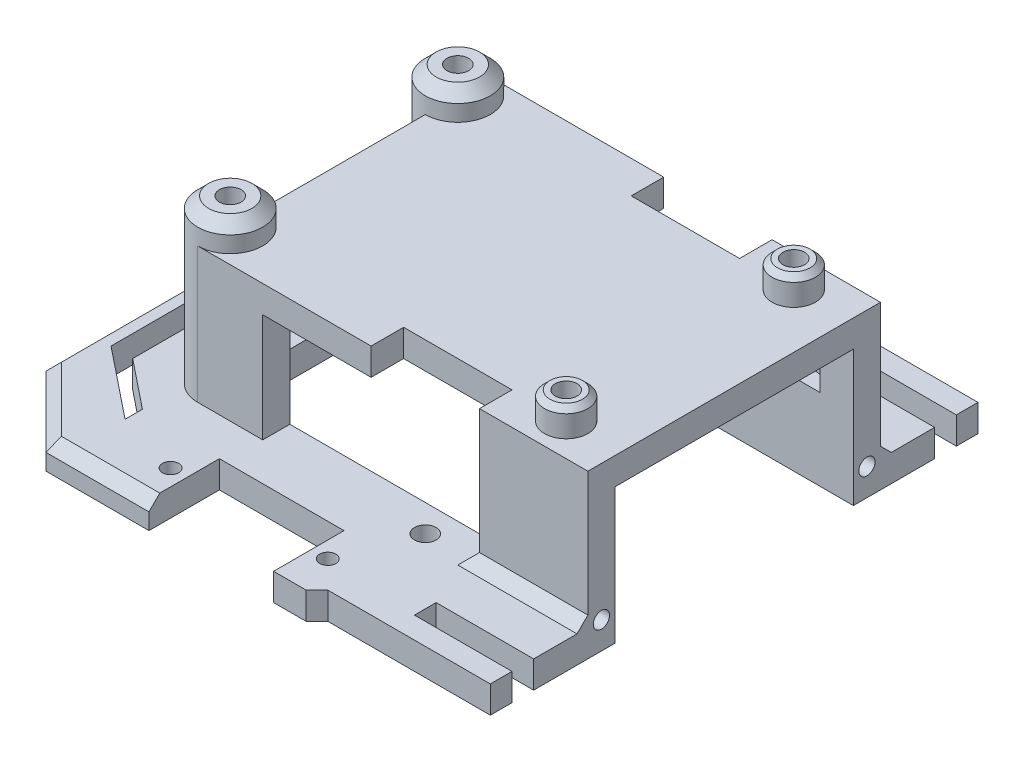
SolidWorks part; units mm, degrees
note: The reader was unsure of these and kept them because the rebuilt part matched: shared geometry of "Sketch13<3>", "Sketch13<5>".
material "Plain Carbon Steel"
ref_plane "Front Plane" through (0, 0, 0) normal (0, 0, 1) x (1, 0, 0)
ref_plane "Top Plane" through (0, 0, 0) normal (0, 1, 0) x (1, 0, 0)
ref_plane "Right Plane" through (0, 0, 0) normal (1, 0, 0) x (0, 0, -1)
sketch "Sketch1" plane through (0, 0, 0) normal (0, 1, 0) x (1, 0, 0)
  line L0 (0, 0) -> (148.3177, 0) construction
  line L1 (0, 34) -> (0, -34)
  line L2 (0, -34) -> (13, -47)
  line L3 (13, -47) -> (32, -47)
  line L4 (32, -47) -> (32, -34)
  line L5 (32, -34) -> (55, -34)
  line L6 (55, -34) -> (55, -47)
  line L7 (55, -47) -> (61, -47)
  line L8 (61, -47) -> (63, -45)
  line L9 (63, -45) -> (93, -45)
  line L10 (93, -45) -> (93, -41)
  line L11 (93, -41) -> (75, -41)
  line L12 (75, -41) -> (75, -37)
  line L13 (75, -37) -> (93, -37)
  line L14 (93, -37) -> (93, -22)
  line L15 (93, -22) -> (33, -22)
  line L16 (33, -22) -> (21, -10)
  line L17 (21, -10) -> (21, 10)
  line L18 (33, 22) -> (21, 10)
  line L19 (93, 22) -> (33, 22)
  line L20 (93, 37) -> (93, 22)
  line L21 (75, 37) -> (93, 37)
  line L22 (75, 41) -> (75, 37)
  line L23 (93, 41) -> (75, 41)
  line L24 (93, 45) -> (93, 41)
  line L25 (63, 45) -> (93, 45)
  line L26 (61, 47) -> (63, 45)
  line L27 (55, 47) -> (61, 47)
  line L28 (55, 34) -> (55, 47)
  line L29 (32, 34) -> (55, 34)
  line L30 (32, 47) -> (32, 34)
  line L31 (13, 47) -> (32, 47)
  line L32 (0, 34) -> (13, 47)
  circle A0 centre (13, -10) radius 2
  circle A1 centre (29, -40) radius 1.5
  circle A2 centre (58, -40) radius 1.5
  circle A3 centre (63, -27) radius 2
  circle A4 centre (13, 10) radius 2
  circle A5 centre (29, 40) radius 1.5
  circle A6 centre (58, 40) radius 1.5
  circle A7 centre (63, 27) radius 2
  point P22 (21, 0)
  dimension "D17" = 4
  dimension "D18" = 3
  dimension "D19" = 4
  dimension "D20" = 3
  dimension "D1" = 34
  dimension "D2" = 13
  dimension "D3" = 22
  dimension "D4" = 37
  dimension "D5" = 23
  dimension "D6" = 2
  dimension "D7" = 6
  dimension "D8" = 2
  dimension "D9" = 43
  dimension "D10" = 4
  dimension "D11" = 93
  dimension "D12" = 10
  dimension "D13" = 45
  dimension "D14" = 72
  dimension "D15" = 43
  dimension "D16" = 61
  dimension "D21" = 3
  dimension "D22" = 10
  dimension "D23" = 3
  dimension "D24" = 30
  dimension "D25" = 54
  dimension "D26" = 6
  dimension "D27" = 6
  dimension "D28" = 80
extrude "Boss-Extrude1" add sketch "Sketch1" along normal blind 5
sketch "Sketch2" plane through (0, 5, 0) normal (0, 1, 0) x (1, 0, 0)
  line L0 (0, 0) -> (79.458, 0) construction
  line L1 (4, 26) -> (4, 12)
  line L2 (8, -8) -> (4, -8)
  line L3 (8, -8) -> (8, 8)
  line L4 (8, 8) -> (4, 8)
  line L5 (4, -8) -> (4, 8)
  line L6 (8, -8) -> (4, 8) construction
  line L7 (8, 8) -> (4, -8) construction
  line L8 (4, 12) -> (8, 12)
  line L9 (8, 12) -> (8, 26)
  line L10 (8, 26) -> (17, 33.2058)
  line L11 (17, 33.2058) -> (17, 36.4083)
  line L12 (17, 36.4083) -> (4, 26)
  line L14 (32, 34) -> (32, 47) construction
  line L16 (0, 34) -> (0, -34) construction
  line L18 (8, -8) -> (4, 8) construction
  line L19 (8, 8) -> (4, -8) construction
  line L20 (17, -36.4083) -> (4, -26)
  line L21 (4, -12) -> (8, -12)
  line L22 (8, -8) -> (4, -8)
  line L23 (8, 8) -> (4, 8)
  line L24 (8, -26) -> (17, -33.2058)
  line L25 (8, -12) -> (8, -26)
  line L26 (4, -26) -> (4, -12)
  line L27 (17, -33.2058) -> (17, -36.4083)
  circle A0 centre (13, 10) radius 2 construction
  point P3 (6, 0)
  dimension "D1" = 2
  dimension "D2" = 2
  dimension "D3" = 4
  dimension "D4" = 2.5
  dimension "D5" = 15
  dimension "D6" = 26
  dimension "D7" = 4
extrude "Cut-Extrude1" cut sketch "Sketch2" against normal blind 5 contours L11 L12 L1 L8 L9 L10 | L5 L2 L3 L4 | L27 L24 L25 L21 L26 L20
sketch "Sketch3" plane through (0, 5, 0) normal (0, 1, 0) x (1, 0, 0)
  line L0 (93, -22) -> (33, -22) construction
  line L1 (33, 22) -> (93, 22) construction
  line L2 (93, -22) -> (33, -22)
  line L3 (33, 22) -> (93, 22)
  line L4 (93, -27) -> (21, -27)
  line L5 (21, 27) -> (93, 27)
  line L6 (21, -10) -> (21, 10) construction
  line L7 (21, -27) -> (21, 27)
  line L8 (33, 27) -> (93, 27) construction
  line L9 (93, -27) -> (33, -27) construction
  line L10 (93, -37) -> (93, -22) construction
  line L11 (93, 22) -> (93, 37) construction
  line L12 (33, -22) -> (21, -10) construction
  line L13 (21, 10) -> (33, 22) construction
  line L14 (93, -27) -> (93, -22)
  line L15 (93, 22) -> (93, 27)
  line L16 (33, -22) -> (21, -10)
  line L17 (21, 10) -> (33, 22)
  dimension "D1" = 5
extrude "Boss-Extrude3" add sketch "Sketch3" along normal blind 25 from surface at 0 contours L7 L17 L3 L15 L5 | L2 L16 L7 L4 L14 starting at face at (9.6667, 5, -24.269)
sketch "Sketch4" plane through (0, 30, 0) normal (0, 1, 0) x (1, 0, 0)
  line L1 (21, 27) -> (93, 27)
  line L2 (21, 27) -> (21, -27)
  line L3 (21, -27) -> (93, -27)
  line L4 (93, 27) -> (93, -27)
extrude "Boss-Extrude4" add sketch "Sketch4" against normal blind 5
sketch "Sketch5" plane through (0, 0, 27) normal (0, 0, 1) x (1, 0, 0)
  line L0 (63, 5) -> (93, 5) construction
  line L1 (33, 25) -> (73, 25)
  line L2 (33, 25) -> (33, 5)
  line L3 (33, 5) -> (73, 5)
  line L4 (73, 25) -> (73, 5)
  line L7 (32, 5) -> (32, 0) construction
  dimension "D1" = 20
  dimension "D2" = 40
  dimension "D3" = 1
extrude "Cut-Extrude2" cut sketch "Sketch5" against normal through all
sketch "Sketch6" plane through (0, 30, 0) normal (0, 1, 0) x (1, 0, 0)
  line L0 (93, 27) -> (21, 27) construction
  line L1 (73, 27) -> (53, 27)
  line L2 (73, 27) -> (73, 21)
  line L3 (73, 21) -> (53, 21)
  line L4 (53, 27) -> (53, 21)
  line L5 (73, 27) -> (73, 22) construction
  line L6 (21, 0) -> (93, 0)
  line L7 (21, 27) -> (21, -27) construction
  line L8 (93, 27) -> (93, -27) construction
  line L9 (53, -27) -> (53, -21)
  line L10 (73, -21) -> (53, -21)
  line L11 (73, -27) -> (73, -21)
  line L12 (73, -27) -> (53, -27)
  line M5 (21, -27) -> (93, -27)
  line M7 (93, 27) -> (21, 27)
  dimension "D1" = 20
  dimension "D2" = 6
extrude "Cut-Extrude4" cut sketch "Sketch6" against normal blind 10 contours L4 L3 L2 M7 | L11 L10 L9 M5
sketch "Sketch7" plane through (0, 25, 0) normal (0, -1, 0) x (1, 0, 0)
  line L1 (93, 22) -> (93, -22) construction
  line L2 (21, 0) -> (93, 0) construction
  line L3 (21, 10) -> (21, -10) construction
  circle A0 centre (83, 21) radius 4
  circle A1 centre (83, -21) radius 4
  dimension "D1" = 8
  dimension "D2" = 10
  dimension "D3" = 21
extrude "Boss-Extrude5" add sketch "Sketch7" against normal blind 5 from surface at -5 starting at face at (61, 30, 0)
sketch "Sketch8" plane through (0, 35, 0) normal (0, 1, 0) x (1, 0, 0)
  circle A0 centre (83, 21) radius 2
  dimension "D1" = 4
extrude "Cut-Extrude5" cut sketch "Sketch8" against normal up to surface (10 mm away) contours A0 up to face at (54, 25, 0)
sketch "Sketch9" plane through (0, 25, 0) normal (0, -1, 0) x (1, 0, 0)
  circle A0 centre (83, -21) radius 4
  dimension "D1" = 8
extrude "Cut-Extrude6" cut sketch "Sketch9" along normal blind 10
sketch "Sketch10" plane through (0, 30, 0) normal (0, 1, 0) x (1, 0, 0)
  line L1 (53, 27) -> (21, 27) construction
  line L2 (21, 27) -> (21, -27) construction
  circle A0 centre (21, 21) radius 6
  dimension "D1" = 12
extrude "Boss-Extrude6" add sketch "Sketch10" against normal blind 30 from offset 5
sketch "Sketch11" plane through (0, 35, 0) normal (0, 1, 0) x (1, 0, 0)
  circle A0 centre (21, 21) radius 2
  dimension "D1" = 4
extrude "Cut-Extrude7" cut sketch "Sketch11" against normal blind 10 contours A0
sketch "Sketch12" plane through (0, 5, 0) normal (0, 1, 0) x (1, 0, 0)
  circle A0 centre (21, 21) radius 4.5
  dimension "D1" = 9
extrude "Cut-Extrude8" cut sketch "Sketch12" against normal through all from surface at 20 starting at face at (21, 25, -19)
sketch "Sketch13" plane through (93, 0, 0) normal (1, 0, 0) x (0, 0, -1)
  line L0 (22, 5) -> (22, 0) construction
  line L1 (27, 5) -> (37, 5) construction
  circle A0 centre (24.5, 5) radius 1.5
  dimension "D2" = 3
  dimension "D1" = 2.5
mirror "Mirror11" about plane through (0, 0, 0) normal (0, 0, 1) of "Cut-Extrude5", "Cut-Extrude6"
mirror "Mirror12" about plane through (0, 0, 0) normal (0, 0, 1) of "Boss-Extrude6"
mirror "Mirror16" about plane through (0, 0, 0) normal (0, 0, 1) of "Cut-Extrude7"
sketch "Sketch14" plane through (0, 25, 0) normal (0, 1, 0) x (1, 0, 0)
  circle A0 centre (21, -21) radius 4.5
  dimension "D1" = 9
extrude "Cut-Extrude11" cut sketch "Sketch14" along direction (0, 1, 0) on the side against the normal through all
extrude "Boss-Extrude8" add sketch "Sketch13" along normal blind 3 contours A0
mirror "Mirror19" about plane through (0, 0, 0) normal (0, 0, 1) of "Boss-Extrude8"
chamfer "Chamfer2" distance 1 angle 45 2 edges at (83, 35, -25) (83, 35, 17)
chamfer "Chamfer3" distance 2 angle 45 7 edges at (22.5, 5, -47) (6.5, 5, -40.5) (0, 5, 0) (6.5, 5, 40.5) (22.5, 5, 47) (21, 35, -15) (21, 35, 15)
chamfer "Chamfer4" distance 2 angle 45 4 edges at (83, 5, -27) (83, 5, 27) (73, 5, 24.5) (73, 5, -24.5)
chamfer "Chamfer5" distance 2 angle 45 2 edges at (83, 25, -19) (83, 25, 23)
sketch "Sketch16" plane through (96, 0, 0) normal (1, 0, 0) x (0, 0, -1)
extrude "Cut-Extrude15" cut sketch "Sketch13<3>" against normal blind 3
sketch "Sketch13<3>" plane through (93, 0, 0) normal (1, 0, 0) x (0, 0, -1) same geometry as "Sketch13"
extrude "Cut-Extrude18" cut sketch "Sketch13<5>" against normal blind 6 from surface at 3 starting at face at (96, 5, -26)
sketch "Sketch13<5>" plane through (93, 0, 0) normal (1, 0, 0) x (0, 0, -1) same geometry as "Sketch13"
sketch "Sketch23" plane through (96, 0, 0) normal (1, 0, 0) x (0, 0, -1)
  circle A0 centre (-24.5, 5) radius 1.5
extrude "Cut-Extrude19" cut sketch "Sketch23" against normal blind 6
